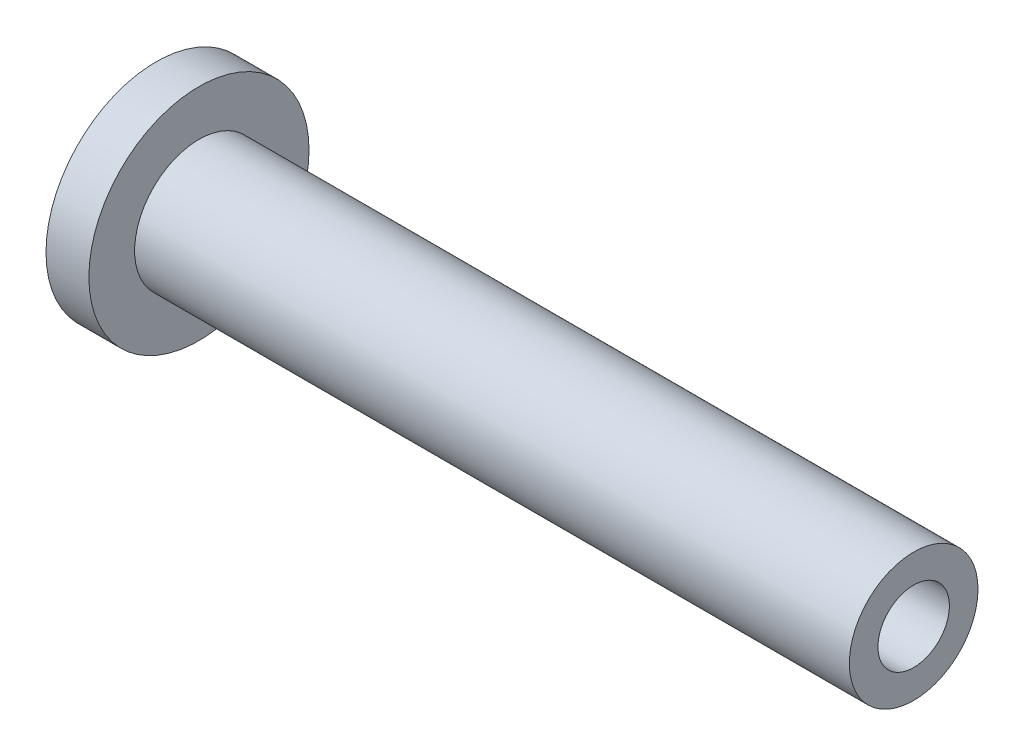
SolidWorks part; units mm, degrees
material "AISI 1020"
ref_plane "Front Plane" through (0, 0, 0) normal (0, 0, 1) x (1, 0, 0)
ref_plane "Top Plane" through (0, 0, 0) normal (0, 1, 0) x (1, 0, 0)
ref_plane "Right Plane" through (0, 0, 0) normal (1, 0, 0) x (0, 0, -1)
sketch "Sketch1" plane through (0, 0, 0) normal (0, 0, 1) x (1, 0, 0)
  line L0 (0, 0) -> (0, 7.7)
  line L1 (0, 7.7) -> (3, 7.7)
  line L2 (3, 7.7) -> (3, 4.5)
  line L3 (3, 4.5) -> (53, 4.5)
  line L4 (53, 4.5) -> (53, 0)
  line L5 (53, 0) -> (0, 0)
  line L6 (0, 0) -> (-5.4432, 0) construction
  dimension "D1" = 50
  dimension "D2" = 3
  dimension "D3" = 9
  dimension "D4" = 15.4
revolve "Revolve1" add sketch "Sketch1" angle 360 about L6
hole_wizard "Broca de rosquear para tarraxa de M61" positions "Esboço1" profile "Esboço2" hole size "M6" standard "ISO"
sketch "Esboço1" plane through (53, 0, 0) normal (1, 0, 0) x (0, 0, -1)
  point P0 (0, 0)
sketch "Esboço2" plane through (53, 0, 0) normal (0, 1, 0) x (0, 0, -1)
  line L0 (0, 0) -> (0, 12.5022)
  line L1 (0, 12.5022) -> (2.5, 11)
  line L2 (2.5, 11) -> (2.5, 0)
  line L5 (2.5, 0) -> (0, 0)
  line L10 (0, 12.5022) -> (-2.5, 11) construction
  line L11 (0, -6.35) -> (0, 107.95) construction
  dimension "Hole Dia." = 5
  dimension "Hole Depth" = 11
  dimension "Drill Angle" = 118
cosmetic thread "Representação de rosca1"
